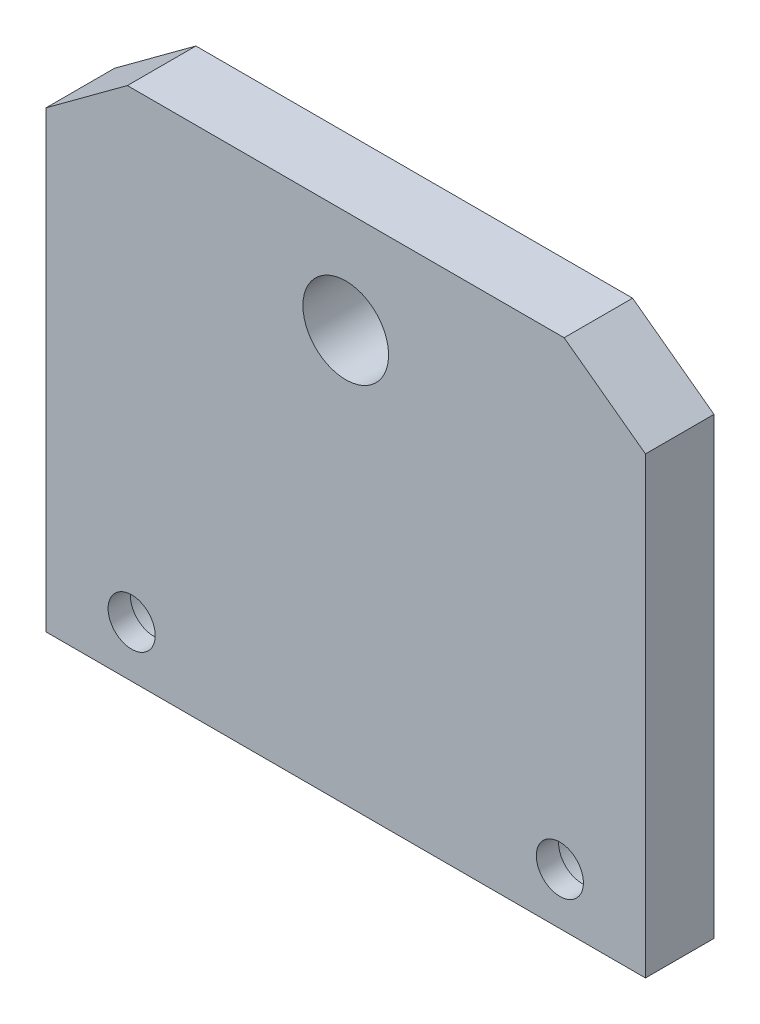
SolidWorks part; units mm, degrees
ref_plane "Front Plane" through (0, 0, 0) normal (0, 0, 1) x (1, 0, 0)
ref_plane "Top Plane" through (0, 0, 0) normal (0, 1, 0) x (1, 0, 0)
ref_plane "Right Plane" through (0, 0, 0) normal (1, 0, 0) x (0, 0, -1)
sketch "Sketch1" plane through (0, 0, 0) normal (0, 0, 1) x (1, 0, 0)
  line L0 (-48.2329, 45.1684) -> (-57.7329, 38.1684) construction
  line L1 (-57.7329, 45.1684) -> (12.2671, 45.1684)
  line L2 (-57.7329, 45.1684) -> (-57.7329, -14.8316)
  line L3 (-57.7329, -14.8316) -> (12.2671, -14.8316)
  line L4 (12.2671, 45.1684) -> (12.2671, -14.8316)
  line L5 (2.7671, 45.1684) -> (12.2671, 38.1684) construction
  line L6 (-22.7329, 45.1684) -> (-22.7329, -14.8316) construction
  circle A0 centre (-47.7329, -8.8316) radius 2.75
  circle A1 centre (2.2671, -8.8316) radius 2.75
  circle A2 centre (-47.7329, -8.8316) radius 5
  circle A3 centre (2.2671, -8.8316) radius 5
  circle A4 centre (-22.7329, 33.1684) radius 5
  dimension "D7" = 5.5
  dimension "D8" = 5.5
  dimension "D9" = 10
  dimension "D10" = 10
  dimension "D16" = 10
  dimension "D1" = 60
  dimension "D2" = 70
  dimension "D3" = 6
  dimension "D4" = 10
  dimension "D5" = 6
  dimension "D6" = 10
  dimension "D11" = 9.5
  dimension "D12" = 7
  dimension "D13" = 9.5
  dimension "D14" = 7
  dimension "D15" = 35
  dimension "D17" = 48
extrude "Boss-Extrude2" add sketch "Sketch1" along normal blind 8 contours L2 L3 L4 L1
extrude "Cut-Extrude3" cut sketch "Sketch1<5>" against normal blind 30 and the other way blind 37 contours A0
sketch "Sketch1<5>" plane through (0, 0, 0) normal (0, 0, 1) x (1, 0, 0) same geometry as "Sketch1"
extrude "Cut-Extrude4" cut sketch "Sketch1<7>" along normal blind 30 and the other way blind 30 contours A1
sketch "Sketch1<7>" plane through (0, 0, 0) normal (0, 0, 1) x (1, 0, 0) same geometry as "Sketch1"
extrude "Cut-Extrude5" cut sketch "Sketch1<8>" along normal blind 42 and the other way blind 88 contours A4
sketch "Sketch1<8>" plane through (0, 0, 0) normal (0, 0, 1) x (1, 0, 0) same geometry as "Sketch1"
sketch "Sketch3" plane through (0, 0, 8) normal (0, 0, 1) x (1, 0, 0)
  line L0 (-48.2329, 45.1684) -> (-57.7329, 38.1684)
  line L1 (-48.2329, 45.1684) -> (-57.7329, 45.1684)
  line L2 (-57.7329, 45.1684) -> (-57.7329, 38.1684)
  line L3 (2.7671, 45.1684) -> (12.2671, 38.1684)
  line L4 (12.2671, 38.1684) -> (12.2671, 45.1684)
  line L5 (12.2671, 45.1684) -> (2.7671, 45.1684)
extrude "Cut-Extrude6" cut sketch "Sketch3" against normal blind 42
extrude "Cut-Extrude7" cut sketch "Sketch1<9>" along normal blind 5.4 contours A2
sketch "Sketch1<9>" plane through (0, 0, 0) normal (0, 0, 1) x (1, 0, 0) same geometry as "Sketch1"
extrude "Cut-Extrude8" cut sketch "Sketch1<10>" along normal blind 5.4 contours A3
sketch "Sketch1<10>" plane through (0, 0, 0) normal (0, 0, 1) x (1, 0, 0) same geometry as "Sketch1"
